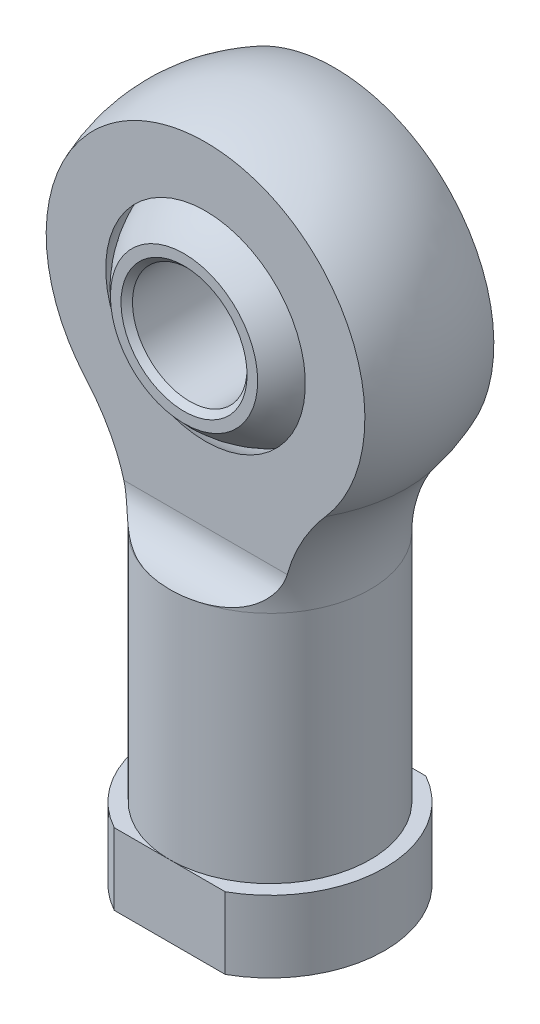
SolidWorks part; units mm, degrees
ref_plane "Front" through (0, 0, 0) normal (0, 0, 1) x (1, 0, 0)
ref_plane "Top" through (0, 0, 0) normal (0, 1, 0) x (1, 0, 0)
ref_plane "Right" through (0, 0, 0) normal (1, 0, 0) x (0, 0, -1)
sketch "Sketch1" plane through (0, 0, 0) normal (0, 0, 1) x (1, 0, 0)
  line L0 (0, 0) -> (0, -17) construction
  line L1 (0, -17) -> (4, -17) construction
  line L2 (4, -17) -> (4, 0) construction
  line L3 (4, 0) -> (0, 0) construction
  line L5 (0, 31) -> (0, 0) construction
  line L6 (0, 31) -> (12, 31) construction
  line L7 (12, 31) -> (12, 19) construction
  line L8 (-4, -17) -> (-4, 0) construction
  line L9 (7, 4.3371) -> (7, -12)
  line L10 (7, -12) -> (8, -12)
  line L11 (8, -12) -> (8, -17)
  line L12 (8, -17) -> (0, -17)
  line L13 (0, -17) -> (0, 4.3371)
  line L14 (0, 4.3371) -> (7, 4.3371)
  line L15 (0, 7) -> (7.2992, 7) construction
  arc A0 (9.5, 11.6686) -> (0, 31) centre (0, 19) ccw construction
  circle A1 centre (0, 19) radius 4 construction
  circle A2 centre (0, 19) radius 7.9 construction
  circle A3 centre (0, 19) radius 8.295 construction
  arc A4 (9.5, 11.6686) -> (0, 7) centre (0, 19) cw construction
  arc A5 (9.5, 11.6686) -> (7, 4.3371) centre (19, 4.3371) ccw construction
  dimension "A" = 8
  dimension "Ball Dia" = 15.8
  dimension "B" = 24
  dimension "D1" = 16.59
  dimension "D" = 36
  dimension "E" = 17
  dimension "Wrench Flats" = 14
  dimension "Base Dia" = 16
  dimension "Base Height" = 5
  dimension "Thread Dia" = 8
revolve "Revolve1" add sketch "Sketch1" angle 360 about L5
sketch "Sketch12" plane through (0, 0, 0) normal (0, 0, 1) x (1, 0, 0)
  line L1 (0, 0) -> (0, 4.3371) construction
  line L2 (8, -17) -> (0, -17) construction
  line L3 (4, -17) -> (4, 0) construction
  line L4 (4, 0) -> (0, 0) construction
  line L5 (4, -17) -> (0, -17)
  line L6 (4, -17) -> (4, 0)
  line L7 (4, 0) -> (0, 0)
  line L8 (0, -17) -> (0, 4.3371) construction
  line L9 (0, -17) -> (0, 0)
revolve "Revolve4" add sketch "Sketch12" angle 360 about L1
sketch "Sketch15" plane through (0, -17, 0) normal (0, -1, 0) x (1, 0, 0)
  circle A1 centre (0, 0) radius 4
  circle A2 centre (0, 0) radius 4
  dimension "D1" = 0
curve "Helix/Spiral1" pitch 2 height 50 turns 25 parameters "pitch"=2
sketch "Sketch16" plane through (0, 0, 0) normal (0, 0, 1) x (1, 0, 0)
  line L0 (4, -17) -> (2.701, -17.75)
  line L1 (2.701, -17.75) -> (2.701, -18)
  line L2 (2.701, -18) -> (4, -18.75)
  line L3 (4, -18.75) -> (4, -17)
  line L4 (2.701, -17.875) -> (4, -17.875) construction
  line L5 (3.3505, -17.375) -> (3.3505, -18.375) construction
  line L6 (-4, -17) -> (4, -17) construction
  dimension "D1" = 60
  dimension "D2" = 0.25
  dimension "D3" = 1
sweep "Cut-Sweep1" cut profiles "Sketch16" path "Helix/Spiral1"
sketch "Sketch14" plane through (0, -12, 0) normal (0, 1, 0) x (-1, 0, 0)
  line L0 (-7, 0) -> (7, 0) construction
  line L1 (7, 7) -> (-7, 7)
  line L2 (7, 7) -> (7, -7) construction
  line L3 (7, -7) -> (-7, -7)
  line L4 (-7, 7) -> (-7, -7) construction
  line L5 (-7, -7) -> (-7, -8)
  line L6 (-7, -8) -> (7, -8)
  line L7 (7, -8) -> (7, -7)
  line L8 (7, 7) -> (7, 8)
  line L9 (7, 8) -> (-7, 8)
  line L10 (-7, 8) -> (-7, 7)
  circle A0 centre (0, 0) radius 8 construction
extrude "Cut-Extrude5" cut sketch "Sketch14" against normal through all and the other way through all
combine bodies "Combine1" operation type subtract main body 123 bodies to subtract 124
sketch "Sketch17" plane through (0, -17, 0) normal (0, -1, 0) x (1, 0, 0)
  circle A1 centre (0, 0) radius 4
  circle A2 centre (0, 0) radius 4
  dimension "D1" = 0
extrude "Extrude1" cut sketch "Sketch17" against normal through all draft 45
sketch "Sketch4" plane through (0, 0, 0) normal (0, 0, 1) x (1, 0, 0)
  line L0 (0, 10.705) -> (0, 4.3371)
  line L3 (7, 4.3371) -> (0, 4.3371)
  line L4 (0, 31) -> (0, 0) construction
  line L5 (0, 31) -> (0, 27.295)
  line L6 (0, 31) -> (0, 33.54) construction
  arc A0 (9.5, 11.6686) -> (0, 31) centre (0, 19) ccw construction
  arc A1 (9.5, 11.6686) -> (0, 31) centre (0, 19) ccw
  arc A2 (9.5, 11.6686) -> (7, 4.3371) centre (19, 4.3371) ccw construction
  arc A3 (9.5, 11.6686) -> (7, 4.3371) centre (19, 4.3371) ccw
  circle A4 centre (0, 19) radius 8.295 construction
  arc A5 (0, 10.705) -> (0, 27.295) centre (0, 19) ccw
  dimension "D1" = 2.54
revolve "Revolve2" add sketch "Sketch4" angle 360 about L6
sketch "Sketch5" plane through (0, 0, 0) normal (1, 0, 0) x (0, 0, -1)
  line L0 (4.5, 31) -> (12, 31)
  line L1 (-4.5, 31) -> (4.5, 31) construction
  line L2 (-4.5, 31) -> (-4.5, 4.3371)
  line L3 (-4.5, 4.3371) -> (4.5, 4.3371) construction
  line L4 (4.5, 31) -> (4.5, 4.3371)
  line L5 (12, 31) -> (12, 4.3371)
  line L6 (12, 4.3371) -> (4.5, 4.3371)
  line L7 (-4.5, 4.3371) -> (-12, 4.3371)
  line L8 (-12, 4.3371) -> (-12, 31)
  line L9 (-12, 31) -> (-4.5, 31)
  line L11 (-7, 4.3371) -> (-7, -12) construction
  arc A0 (9.5, 11.6686) -> (-9.5, 11.6686) centre (0, 19) ccw construction
  dimension "D1" = 2.5
  dimension "F" = 9
extrude "Cut-Extrude1" cut sketch "Sketch5" against normal through all and the other way through all
fillet "Fillet1" radius 2.5 2 edges at (0, 4.3371, 4.5) (0, 4.3371, -4.5)
sketch "Sketch7" plane through (0, 0, 0) normal (0, 0, 1) x (1, 0, 0)
  line L0 (0, 26.9) -> (0, 11.1)
  line L1 (0, 31) -> (0, 0) construction
  line L2 (0, 0) -> (0, 11.1) construction
  arc A0 (0, 11.1) -> (0, 26.9) centre (0, 19) ccw
  circle A1 centre (0, 19) radius 7.9 construction
revolve "Revolve3" add sketch "Sketch7" angle 360 about L2
sketch "Sketch8" plane through (0, 0, 0) normal (1, 0, 0) x (0, 0, -1)
  line L0 (-4.5, 31) -> (4.5, 31) construction
  line L1 (-6, 31) -> (6, 31) construction
  line L2 (-6, 31) -> (-6, 4.3371)
  line L3 (-6, 4.3371) -> (6, 4.3371) construction
  line L4 (6, 31) -> (6, 4.3371)
  line L5 (6, 31) -> (12, 31)
  line L6 (12, 31) -> (12, 4.3371)
  line L7 (12, 4.3371) -> (6, 4.3371)
  line L8 (-6, 4.3371) -> (-12, 4.3371)
  line L9 (-12, 4.3371) -> (-12, 31)
  line L10 (-12, 31) -> (-6, 31)
  dimension "C" = 12
extrude "Cut-Extrude3" cut sketch "Sketch8" against normal through all and the other way through all
sketch "Sketch10" plane through (0, 0, 0) normal (0, 0, 1) x (1, 0, 0)
  circle A0 centre (0, 19) radius 4 construction
  circle A1 centre (0, 19) radius 4
extrude "Cut-Extrude4" cut sketch "Sketch10" against normal through all and the other way through all
chamfer "Chamfer1" distance 0.4 angle 45 2 edges at (0, 15, -6) (0, 23, 6)
sketch "Sketch11" plane through (0, 0, 0) normal (1, 0, 0) x (0, 0, -1)
  line L0 (0, 19) -> (-6, 20.9495) construction
  line L1 (-7, -17) -> (7, -17) construction
  line L2 (0, 19) -> (-6, 17.0505) construction
  line L3 (0, 31) -> (0, 0) construction
  line L4 (-6, 31) -> (-6, 4.3371) construction
  line L5 (0, 19) -> (0.0074, 19) construction
  line L6 (-4, 0) -> (4, 0)
  line L7 (-4, 0) -> (-4, -17)
  line L8 (-4, -17) -> (4, -17)
  line L9 (4, 0) -> (4, -17)
  dimension "D1" = 8
equation "\"D1@Sketch1\"=\"Ball Dia@Sketch1\"*1.05"
equation "\"D1@Chamfer1\"=\"A@Sketch1\"/20"
equation "\"D1@Fillet1\"=\"D1@Sketch5\""
equation "\"D2@Sketch16\" = \"pitch@Helix/Spiral1\"*.125"
equation "\"D3@Sketch16\" = \"pitch@Helix/Spiral1\"*.5"
equation "\"D1@Sketch11\" = \"Thread Dia@Sketch1\""
